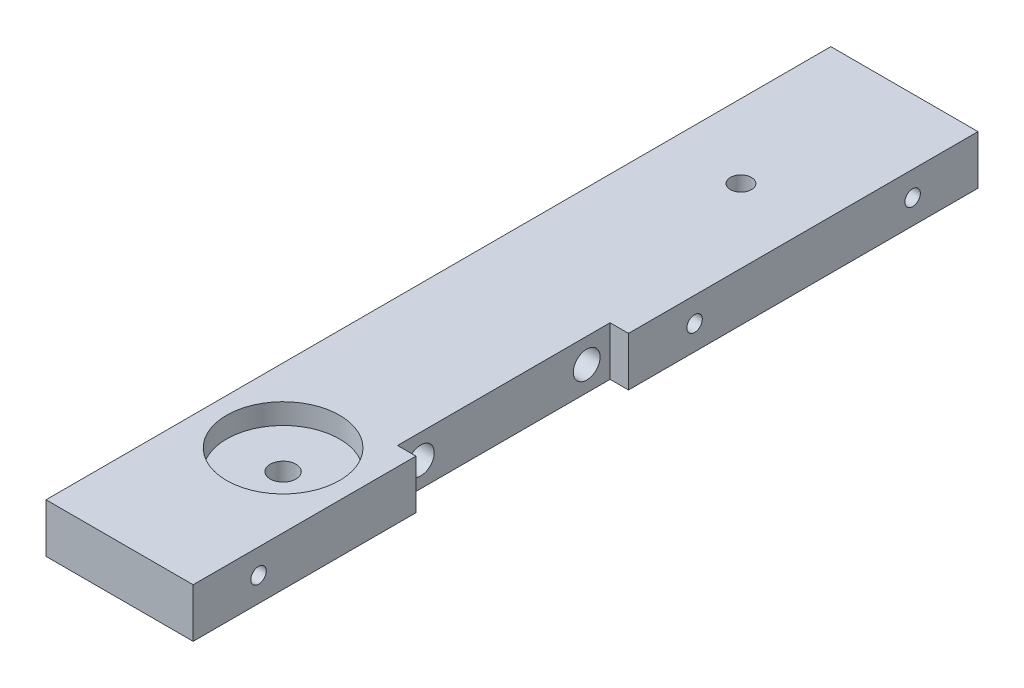
SolidWorks part; units mm, degrees
ref_plane "Front Plane" through (0, 0, 0) normal (0, 0, 1) x (1, 0, 0)
ref_plane "Top Plane" through (0, 0, 0) normal (0, 1, 0) x (1, 0, 0)
ref_plane "Right Plane" through (0, 0, 0) normal (1, 0, 0) x (0, 0, -1)
sketch "Sketch2" plane through (0, 0, 0) normal (0, 1, 0) x (1, 0, 0)
  line L0 (0, 0) -> (0, 152.4)
  line L1 (0, 152.4) -> (28.575, 152.4)
  line L2 (28.575, 152.4) -> (28.575, 0)
  line L3 (28.575, 0) -> (0, 0)
  dimension "D1" = 152.4
  dimension "D2" = 28.575
extrude "Boss-Extrude1" add sketch "Sketch2" along normal blind 9.525
sketch "Sketch3" plane through (0, 0, 0) normal (-1, 0, 0) x (0, 0, 1)
  line L3 (-152.4, 9.525) -> (0, 9.525) construction
  line L4 (-152.4, 9.525) -> (-152.4, 0) construction
  point P6 (-139.7, 4.7625)
  point P14 (-139.7, 4.7625)
  dimension "D1" = 4.7625
  dimension "D2" = 12.7
sketch "Sketch8" plane through (0, 0, 0) normal (-1, 0, 0) x (0, 0, 1)
  point P0 (-139.7, 4.7625)
hole_wizard "Ø3.0mm Dowel Hole1" positions "Sketch8" profile "Sketch9" hole size "Ø3.0" standard "ANSI Metric" end condition through all
sketch "Sketch9" plane through (0, 4.7625, -139.7) normal (0, 1, 0) x (0, 0, 1)
  line L0 (0, 0) -> (0, 28.575)
  line L1 (0, 28.575) -> (1.5, 28.575)
  line L2 (1.5, 28.575) -> (1.5, 0)
  line L5 (1.5, 0) -> (0, 0)
  line L11 (0, -6.35) -> (0, 107.95) construction
  dimension "Thru Hole Dia." = 3
  dimension "Thru Hole Depth" = 28.575
pattern_linear "LPattern1" count 4 spacing 42.3333 along (0, 0, 1) skipping (2, 0) of "Ø3.0mm Dowel Hole1"
sketch "Sketch12" plane through (0, 9.525, 0) normal (0, 1, 0) x (1, 0, 0)
  line L0 (28.575, 0) -> (28.575, 152.4) construction
  line L2 (0, 0) -> (28.575, 0) construction
  circle A1 centre (14.2875, 31.75) radius 10.975
  circle A2 centre (14.2875, 120.65) radius 2.05
  point P0 (14.2875, 120.65)
  point P1 (14.2875, 76.2)
  point P2 (14.2875, 31.75)
  dimension "D8" = 4.1
  dimension "D9" = 21.95
  dimension "D1" = 14.2875
  dimension "D2" = 14.2875
  dimension "D3" = 14.2875
  dimension "D4" = 76.2
  dimension "D5" = 44.45
  dimension "D6" = 44.45
sketch "Sketch13" plane through (0, 0, 0) normal (-1, 0, 0) x (0, 0, 1)
  line L2 (0, 9.525) -> (0, 0) construction
  line L3 (-152.4, 9.525) -> (0, 9.525) construction
  circle A0 centre (-80, 4.7625) radius 2.6
  circle A1 centre (-47.79, 4.7625) radius 2.6
  point P5 (-80, 4.7625)
  point P11 (-47.79, 4.7625)
  dimension "D1" = 80
  dimension "D2" = 4.7625
  dimension "D3" = 32.21
extrude "Cut-Extrude1" cut sketch "Sketch12" against normal through all contours A2
extrude "Cut-Extrude2" cut sketch "Sketch12<4>" against normal blind 4 contours A1
sketch "Sketch12<4>" plane through (0, 9.525, 0) normal (0, 1, 0) x (1, 0, 0) same geometry as "Sketch12"
sketch "Sketch15" plane through (0, 5.525, 0) normal (0, 1, 0) x (1, 0, 0)
  circle A0 centre (14.2875, 31.75) radius 2.5
  dimension "D1" = 5
extrude "Cut-Extrude3" cut sketch "Sketch15" against normal through all
extrude "Cut-Extrude4" cut sketch "Sketch13" against normal through all
sketch "Sketch17" plane through (28.575, 0, 0) normal (-1, 0, 0) x (0, 0, 1)
  line L0 (-152.4, 9.525) -> (0, 9.525) construction
  line L1 (-84.535, 9.525) -> (-43.255, 9.525)
  line L2 (-84.535, 9.525) -> (-84.535, 0)
  line L3 (-84.535, 0) -> (-43.255, 0)
  line L4 (-43.255, 9.525) -> (-43.255, 0)
  line L5 (-152.4, 0) -> (0, 0) construction
  circle A3 centre (-80, 4.7625) radius 2.6 construction
  circle A4 centre (-47.79, 4.7625) radius 2.6 construction
  point P12 (-84.535, 4.7625)
  dimension "D2" = 41.28
  dimension "D1" = 32.21
  dimension "D4" = 4.535
  dimension "D3" = 4.535
extrude "Cut-Extrude5" cut sketch "Sketch17" along normal offset from surface (3.575 mm away) 25 up to face at (0, 4.7625, -77.4)
